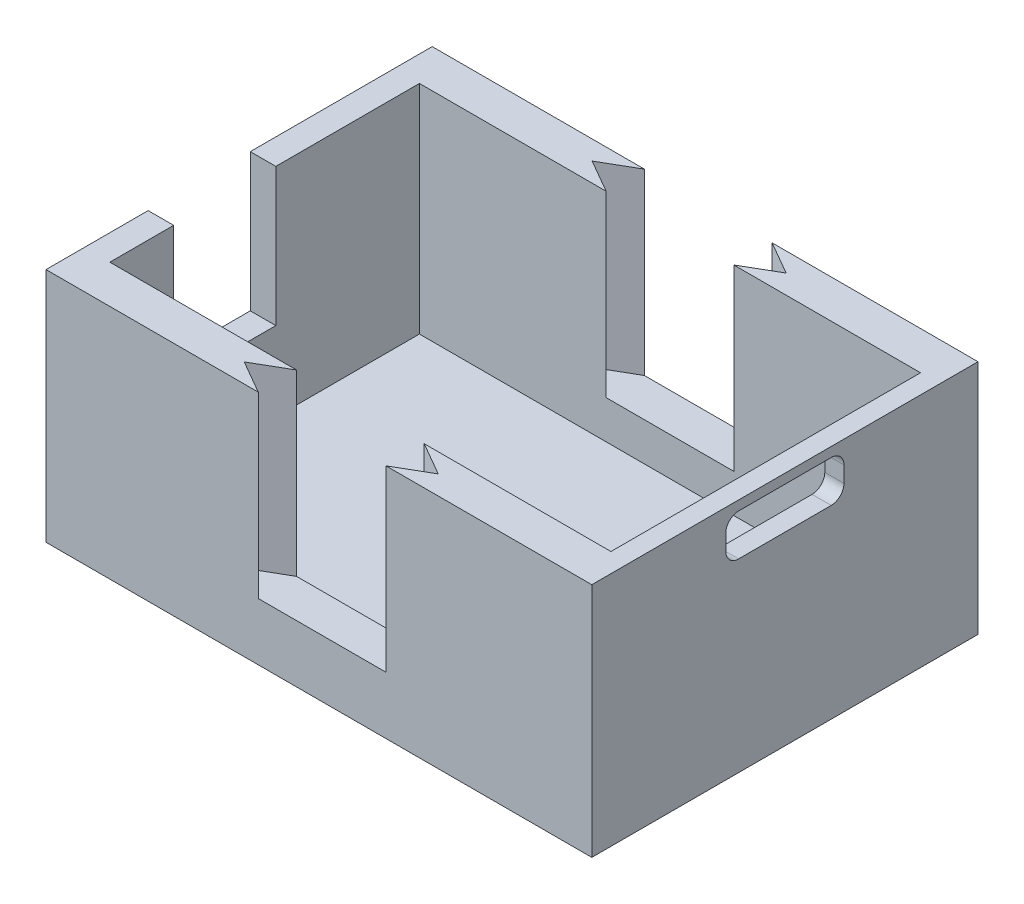
SolidWorks part; units mm, degrees
ref_plane "Front Plane" through (0, 0, 0) normal (0, 0, 1) x (1, 0, 0)
ref_plane "Top Plane" through (0, 0, 0) normal (0, 1, 0) x (1, 0, 0)
ref_plane "Right Plane" through (0, 0, 0) normal (1, 0, 0) x (0, 0, -1)
sketch "Sketch1" plane through (0, 0, 0) normal (0, 1, 0) x (1, 0, 0)
  line L1 (-19.625, -12.125) -> (19.625, -12.125)
  line L2 (-19.625, -12.125) -> (-19.625, 12.125)
  line L3 (-19.625, 12.125) -> (19.625, 12.125)
  line L4 (19.625, -12.125) -> (19.625, 12.125)
  line L5 (-19.625, -12.125) -> (19.625, 12.125) construction
  line L6 (-19.625, 12.125) -> (19.625, -12.125) construction
  point P0 (0, 0)
  dimension "D1" = 39.25
  dimension "D2" = 24.25
extrude "Boss-Extrude1" add sketch "Sketch1" along normal blind 1.5
sketch "Sketch2" plane through (0, 0, 0) normal (0, 1, 0) x (1, 0, 0)
  line L6 (21.125, 15.125) -> (-21.625, 15.125)
  line L9 (21.125, 15.125) -> (21.125, -15.125)
  line L10 (21.125, -15.125) -> (-21.625, -15.125)
  line L11 (-21.625, 15.125) -> (-21.625, -15.125)
  line L13 (19.625, -12.125) -> (19.625, 12.125)
  line L14 (19.625, 12.125) -> (-19.625, 12.125)
  line L15 (-19.625, 12.125) -> (-19.625, -12.125)
  line L16 (-19.625, -12.125) -> (19.625, -12.125)
  line L17 (19.625, -12.125) -> (19.625, 12.125)
  line L18 (19.625, 12.125) -> (-19.625, 12.125)
  line L19 (-19.625, 12.125) -> (-19.625, -12.125)
  line L20 (-19.625, -12.125) -> (19.625, -12.125)
  point P0 (0, 0)
  dimension "D1" = 3
  dimension "D2" = 3
  dimension "D3" = 0
  dimension "D4" = 2
  dimension "D5" = 1.5
extrude "Boss-Extrude2" add sketch "Sketch2" along normal offset from surface (18.5 mm away) 17 up to face at (0, 1.5, 0) offset beyond the face yes
sketch "Sketch3" plane through (0, 18.5, 0) normal (0, 1, 0) x (1, 0, 0)
  line L1 (-19.625, 0.875) -> (-21.625, 0.875)
  line L2 (-19.625, 0.875) -> (-19.625, -7.125)
  line L3 (-19.625, -7.125) -> (-21.625, -7.125)
  line L4 (-21.625, 0.875) -> (-21.625, -7.125)
  line L7 (-19.625, -12.125) -> (19.625, -12.125) construction
  line L8 (-21.625, -15.125) -> (-21.625, 15.125) construction
  line L9 (-19.625, -12.125) -> (-19.625, 12.125) construction
  point P4 (0, 0)
  point P5 (0, 0)
  point P11 (0, 0)
  point P12 (0, 0)
  dimension "D1" = 8
  dimension "D2" = 5
extrude "Cut-Extrude1" cut sketch "Sketch3" against normal offset from surface (10.8 mm away) 6.2 up to face at (0, 1.5, 0)
sketch "Sketch4" plane through (21.125, 0, 0) normal (1, 0, 0) x (0, 0, -1)
  line L1 (-3.625, 14.5) -> (3.625, 14.5)
  line L2 (-4.625, 15.5) -> (-4.625, 16.75)
  line L3 (-3.625, 17.75) -> (3.625, 17.75)
  line L4 (4.625, 15.5) -> (4.625, 16.75)
  line L5 (-4.625, 14.5) -> (4.625, 17.75) construction
  line L6 (-4.625, 17.75) -> (4.625, 14.5) construction
  line L7 (-12.125, 1.5) -> (12.125, 1.5) construction
  arc A0 (-3.625, 14.5) -> (-4.625, 15.5) centre (-3.625, 15.5) cw
  arc A1 (3.625, 14.5) -> (4.625, 15.5) centre (3.625, 15.5) ccw
  arc A2 (3.625, 17.75) -> (4.625, 16.75) centre (3.625, 16.75) cw
  arc A3 (-4.625, 16.75) -> (-3.625, 17.75) centre (-3.625, 16.75) cw
  point P0 (0, 16.125)
  point P7 (0.0279, 16.125)
  dimension "D4" = 1
  dimension "D1" = 13
  dimension "D2" = 3.25
  dimension "D3" = 9.25
extrude "Cut-Extrude2" cut sketch "Sketch4" against normal up to next
sketch "Sketch6" plane through (0, 18.5, 0) normal (0, 1, 0) x (1, 0, 0)
  line L0 (0, 0) -> (0, 18.4461) construction
  line L1 (-5, 15.125) -> (-7.5981, 13.625)
  line L2 (-21.625, 15.125) -> (21.125, 15.125) construction
  line L3 (-7.5981, 13.625) -> (-5, 12.125)
  line L4 (19.625, 12.125) -> (-19.625, 12.125) construction
  line L5 (-5, 15.125) -> (-5, 12.125) construction
  line L6 (-5, 15.125) -> (5, 15.125)
  line L7 (-5, 12.125) -> (5, 12.125)
  line L8 (5, 15.125) -> (5, 12.125) construction
  line L9 (7.5981, 13.625) -> (5, 12.125)
  line L10 (5, 15.125) -> (7.5981, 13.625)
  line L11 (-7.5981, 0) -> (7.5981, 0) construction
  line L12 (-7.5981, -13.625) -> (-5, -12.125)
  line L13 (-5, -15.125) -> (-7.5981, -13.625)
  line L14 (-5, -15.125) -> (5, -15.125)
  line L15 (5, -15.125) -> (7.5981, -13.625)
  line L16 (7.5981, -13.625) -> (5, -12.125)
  line L17 (-5, -12.125) -> (5, -12.125)
  point P7 (-5, 13.625)
  point P16 (0, 12.125)
  point P18 (0, 15.125)
  point P20 (0, 0)
  dimension "D1" = 60
  dimension "D2" = 5
extrude "Cut-Extrude3" cut sketch "Sketch6" against normal offset from surface (14 mm away) 3 up to face at (0, 1.5, 0)
